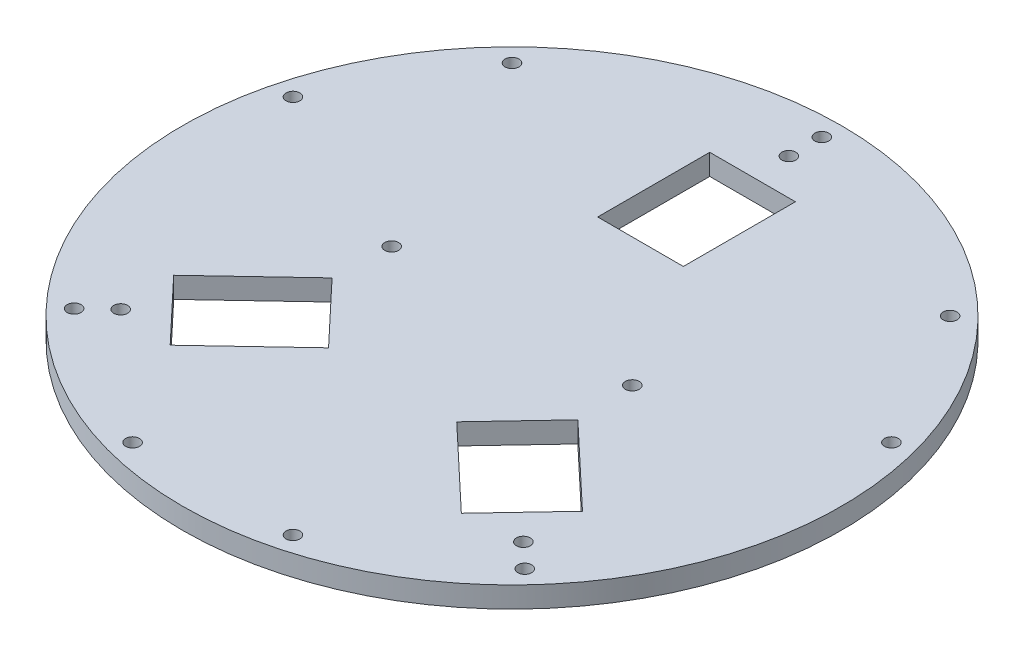
SolidWorks part; units mm, degrees
ref_plane "Front Plane" through (0, 0, 0) normal (0, 0, 1) x (1, 0, 0)
ref_plane "Top Plane" through (0, 0, 0) normal (0, 1, 0) x (1, 0, 0)
ref_plane "Right Plane" through (0, 0, 0) normal (1, 0, 0) x (0, 0, -1)
sketch "Sketch1" plane through (0, 0, 0) normal (0, 1, 0) x (1, 0, 0)
  line L0 (0, 100) -> (0, -100) construction
  line L11 (0, 0) -> (91.8216, 39.608) construction
  line L12 (0, 0) -> (-91.8216, 39.608) construction
  line L13 (19.4464, -36.2193) -> (62.0194, -40.6398) construction
  line L14 (-13, 73) -> (13, 73)
  line L15 (-13, 73) -> (-13, 39)
  line L16 (-13, 39) -> (13, 39)
  line L17 (13, 73) -> (13, 39)
  line L18 (-13, 73) -> (13, 39) construction
  line L19 (-13, 39) -> (13, 73) construction
  line L20 (44.1771, -59.5515) -> (37.2887, -17.3076) construction
  line L21 (62.0194, -40.6398) -> (37.2887, -17.3076)
  line L22 (19.4464, -36.2193) -> (37.2887, -17.3076)
  line L23 (44.1771, -59.5515) -> (19.4464, -36.2193)
  line L24 (44.1771, -59.5515) -> (62.0194, -40.6398)
  line L25 (-37.2887, -17.3076) -> (-44.1771, -59.5515) construction
  line L26 (-62.0194, -40.6398) -> (-19.4464, -36.2193) construction
  line L27 (-44.1771, -59.5515) -> (-19.4464, -36.2193)
  line L28 (-37.2887, -17.3076) -> (-19.4464, -36.2193)
  line L29 (-62.0194, -40.6398) -> (-37.2887, -17.3076)
  line L30 (-62.0194, -40.6398) -> (-44.1771, -59.5515)
  circle A0 centre (0, 0) radius 100
  circle A5 centre (0, 94) radius 2.1
  circle A6 centre (0, 84) radius 2.1
  circle A7 centre (61.0994, -57.6443) radius 2.1
  circle A8 centre (68.3731, -64.5067) radius 2.1
  circle A9 centre (-68.3731, -64.5067) radius 2.1
  circle A10 centre (-61.0994, -57.6443) radius 2.1
  point P29 (0, 56)
  point P38 (40.7329, -38.4295)
  point P43 (-40.7329, -38.4295)
  point P46 (0, 0)
  dimension "D1" = 200
  dimension "D6" = 4.2
  dimension "D2" = 66.667
  dimension "D7" = 6
  dimension "D8" = 10
  dimension "D10" = 34
  dimension "D11" = 26
  dimension "D12" = 11
extrude "Boss-Extrude1" add sketch "Sketch1" along normal blind 6.35
sketch "Sketch2" plane through (0, 6.35, 0) normal (0, 1, 0) x (1, 0, 0)
  line L0 (0, 0) -> (0, -100) construction
  line L1 (0, 0) -> (-25.8819, -96.5926) construction
  circle A0 centre (0, 0) radius 100 construction
  circle A1 centre (-24.329, -90.797) radius 2.1
  circle A2 centre (24.329, -90.797) radius 2.1
  circle A3 centre (-66.468, 66.468) radius 2.1
  circle A4 centre (-90.797, 24.329) radius 2.1
  circle A5 centre (90.797, 24.329) radius 2.1
  circle A6 centre (66.468, 66.468) radius 2.1
  point P22 (0, 0)
  dimension "D4" = 4.2
  dimension "D1" = 15
  dimension "D5" = 6
  dimension "D6" = 3
extrude "Cut-Extrude1" cut sketch "Sketch2" against normal up to surface (6.35 mm away) up to face at (40.7329, 0, 38.4295)
sketch "Sketch3" plane through (0, 6.35, 0) normal (0, 1, 0) x (1, 0, 0)
  line L0 (-100, 0) -> (100, 0) construction
  line L1 (0, -100) -> (0, 100) construction
  circle A0 centre (0, 0) radius 100 construction
  circle A1 centre (36.5, 0) radius 2.1
  circle A2 centre (-36.5, 0) radius 2.1
  dimension "D2" = 4.2
  dimension "D1" = 36.5
extrude "Cut-Extrude2" cut sketch "Sketch3" against normal up to surface (6.35 mm away) up to face at (90.797, 0, -22.229)
